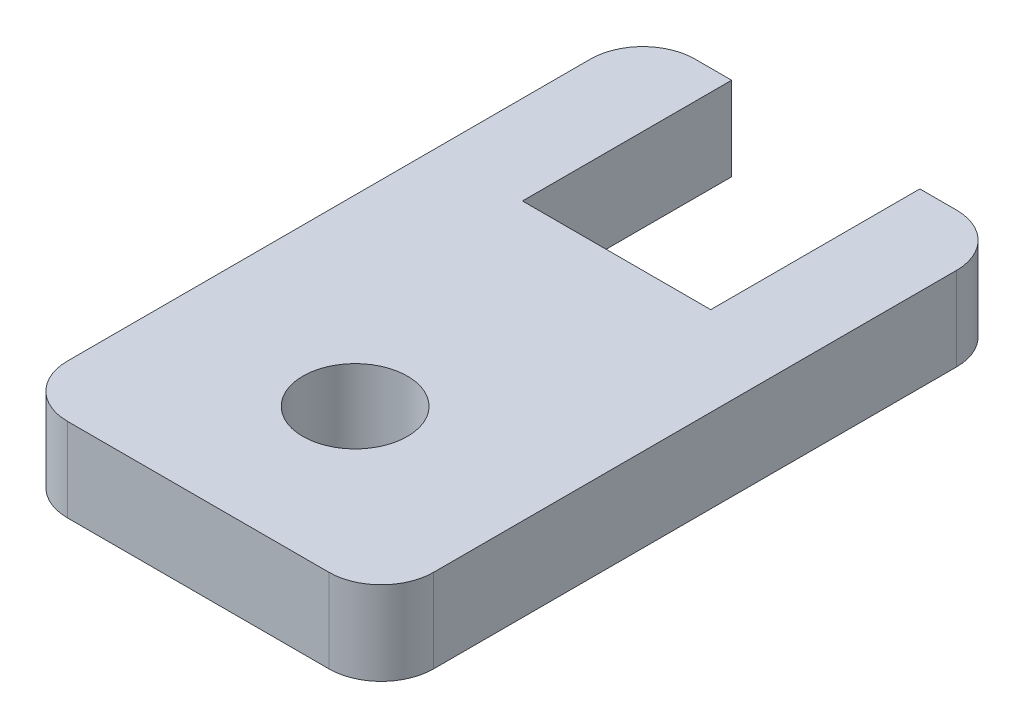
SolidWorks part; units mm, degrees
ref_plane "Front Plane" through (0, 0, 0) normal (0, 0, 1) x (1, 0, 0)
ref_plane "Top Plane" through (0, 0, 0) normal (0, 1, 0) x (1, 0, 0)
ref_plane "Right Plane" through (0, 0, 0) normal (1, 0, 0) x (0, 0, -1)
sketch "Sketch1" plane through (0, 0, 0) normal (0, 1, 0) x (1, 0, 0)
  line L0 (-3.5, 6) -> (3.5, -6) construction
  line L1 (-3.5, 6) -> (3.5, 6)
  line L2 (-3.5, 6) -> (-3.5, -6)
  line L3 (-3.5, -6) -> (3.5, -6)
  line L4 (3.5, 6) -> (3.5, -6)
  line L5 (0, 6) -> (0, -6) construction
  point P4 (0, 0)
  dimension "D1" = 7
  dimension "D2" = 12
extrude "Boss-Extrude1" add sketch "Sketch1" along normal blind 1.6
sketch "Sketch3" plane through (0, 0, 0) normal (0, -1, 0) x (1, 0, 0)
  line L0 (3.5, -6) -> (-3.5, -6) construction
  line L1 (1.8, -6) -> (-1.8, -6)
  line L2 (1.8, -6) -> (1.8, -2)
  line L3 (1.8, -2) -> (-1.8, -2)
  line L4 (-1.8, -6) -> (-1.8, -2)
  line L5 (1.8, -6) -> (-1.8, -2) construction
  line L6 (1.8, -2) -> (-1.8, -6) construction
  point P4 (0, -4)
  point P7 (0, -6)
  dimension "D1" = 3.6
  dimension "D2" = 4
extrude "Cut-Extrude2" cut sketch "Sketch3" against normal through all
sketch "Sketch4" plane through (0, 1.6, 0) normal (0, 1, 0) x (1, 0, 0)
  line L0 (-3.5, -6) -> (3.5, -6) construction
  circle A0 centre (0, -3) radius 1
  dimension "D1" = 2
  dimension "D2" = 3
extrude "Cut-Extrude3" cut sketch "Sketch4" against normal blind 10
fillet "Fillet1" radius 1 4 edges at (3.5, 0.8, -6) (-3.5, 0.8, -6) (-3.5, 0.8, 6) (3.5, 0.8, 6)
sketch "Sketch2" plane through (0, 0, 0) normal (0, -1, 0) x (1, 0, 0)
  line L0 (-1.1068, 5.4814) -> (-1.1068, -5.4972) construction
  text T0 "RBF"
extrude "Cut-Extrude1" [suppressed] cut sketch "Sketch2" against normal blind 0.01
